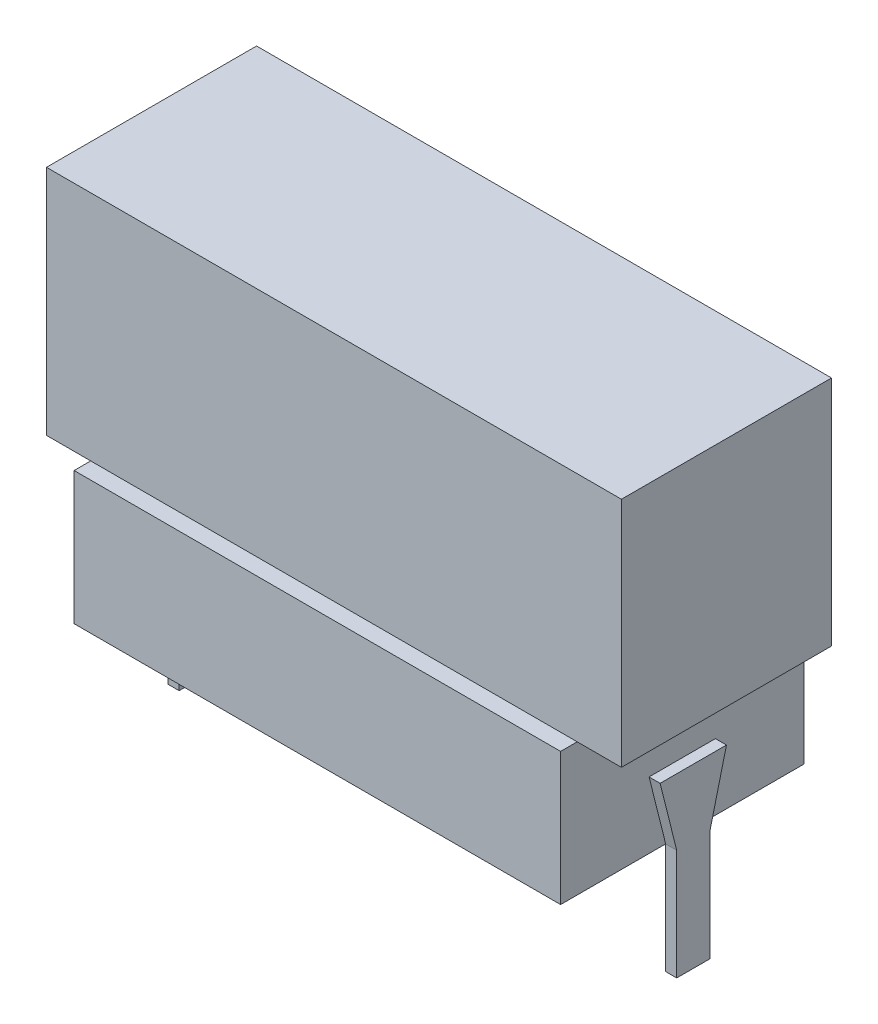
SolidWorks part; units mm, degrees
ref_plane "前视" through (0, 0, 0) normal (0, 0, 1) x (1, 0, 0)
ref_plane "上视" through (0, 0, 0) normal (0, 1, 0) x (1, 0, 0)
ref_plane "右视" through (0, 0, 0) normal (1, 0, 0) x (0, 0, -1)
sketch "草图1" plane through (0, 0, 0) normal (0, 1, 0) x (1, 0, 0)
  line L0 (-28.3755, 0) -> (18.4931, 0) construction
  line L1 (-11, 5.5) -> (11, 5.5)
  line L2 (-11, 5.5) -> (-11, -5.5)
  line L3 (-11, -5.5) -> (11, -5.5)
  line L4 (11, 5.5) -> (11, -5.5)
  line L5 (0, 15.354) -> (0, -11.4281) construction
  dimension "D1" = 22
  dimension "D2" = 11
extrude "凸台-拉伸1" add sketch "草图1" along normal blind 6
sketch "草图3" plane through (11, 11, 0) normal (-1, 0, 0) x (0, -1, 0)
  line L0 (8, 1.5) -> (8, -1.5)
  line L1 (8, -1.5) -> (11, -0.75)
  line L2 (11, 5.5) -> (11, -5.5) construction
  line L3 (11, -0.75) -> (16, -0.75)
  line L4 (16, -0.75) -> (16, 0.75)
  line L5 (16, 0.75) -> (11, 0.75)
  line L6 (11, 0.75) -> (8, 1.5)
  line L7 (9.2948, 0) -> (12.7052, 0) construction
  point P12 (11, 0)
  dimension "D1" = 1.5
  dimension "D2" = 3
  dimension "D3" = 5
  dimension "D4" = 3
extrude "凸台-拉伸3" add sketch "草图3" against normal blind 0.5
mirror "镜向3" about plane through (0, 0, 0) normal (1, 0, 0) of "凸台-拉伸3"
sketch "草图7" plane through (0, 0, 0) normal (1, 0, 0) x (0, 0, -1)
  line L0 (2.9, 6) -> (2.9, 7.4)
  line L1 (5.5, 6) -> (-5.5, 6) construction
  line L2 (0, -19.836) -> (0, 19.836) construction
  line L3 (2.7, 6) -> (2.7, 7.4)
  line L4 (2, 14.3639) -> (1.8673, 14.5136)
  line L5 (2.7, 6) -> (2.9, 6)
  line L6 (-2.7, 6) -> (-2.9, 6)
  line L7 (-2, 14.3639) -> (-1.8673, 14.5136)
  line L8 (-2.7, 6) -> (-2.7, 7.4)
  line L9 (-2.9, 6) -> (-2.9, 7.4)
  arc A0 (2.7, 7.4) -> (2.4537, 7.6952) centre (2.4, 7.4) ccw
  arc A1 (2.0875, 8.8453) -> (2.4894, 7.8919) centre (2.6, 8.5) ccw
  arc A3 (1.9345, 8.9758) -> (2.4537, 7.6952) centre (2.6, 8.5) ccw
  arc A4 (2.9, 7.4) -> (2.4894, 7.8919) centre (2.4, 7.4) ccw
  arc A5 (1.998, 13.2378) -> (2, 14.3639) centre (2.5, 13.8) cw
  arc A6 (2.0875, 8.8453) -> (1.998, 13.2378) centre (0, 11) ccw
  arc A7 (1.9345, 8.9758) -> (1.8648, 13.0886) centre (0, 11) ccw
  arc A8 (1.8648, 13.0886) -> (1.8673, 14.5136) centre (2.5, 13.8) cw
  arc A9 (-1.8648, 13.0886) -> (-1.8673, 14.5136) centre (-2.5, 13.8) ccw
  arc A10 (-1.9345, 8.9758) -> (-1.8648, 13.0886) centre (0, 11) cw
  arc A11 (-2.0875, 8.8453) -> (-1.998, 13.2378) centre (0, 11) cw
  arc A12 (-1.998, 13.2378) -> (-2, 14.3639) centre (-2.5, 13.8) ccw
  arc A13 (-2.9, 7.4) -> (-2.4894, 7.8919) centre (-2.4, 7.4) cw
  arc A14 (-1.9345, 8.9758) -> (-2.4537, 7.6952) centre (-2.6, 8.5) cw
  arc A15 (-2.0875, 8.8453) -> (-2.4894, 7.8919) centre (-2.6, 8.5) cw
  arc A16 (-2.7, 7.4) -> (-2.4537, 7.6952) centre (-2.4, 7.4) cw
  point P18 (0, 0)
  point P37 (0, 0)
  dimension "D2" = 0.5
  dimension "D12" = 3
  dimension "D3" = 2.9
  dimension "D4" = 1.4
  dimension "D5" = 2.5
  dimension "D6" = 2.5
  dimension "D7" = 7.8
  dimension "D8" = 2
  dimension "D9" = 2.6
  dimension "D11" = 5
  dimension "D10" = 0.2
extrude "凸台-拉伸5" add sketch "草图7" along normal mid plane 21
sketch "草图8" plane through (0, 0, 0) normal (0, 0, 1) x (1, 0, 0)
  line L0 (-11, 6) -> (11, 6) construction
  line L1 (-5, 14.5136) -> (5, 14.5136)
  line L2 (-5, 14.5136) -> (-5, 6)
  line L3 (-5, 6) -> (5, 6)
  line L4 (5, 14.5136) -> (5, 6)
  line L5 (10.5, 14.5136) -> (-10.5, 14.5136) construction
  line L6 (0, 0) -> (0, 10.3417) construction
  dimension "D1" = 10
extrude "切除-拉伸1" cut sketch "草图8" against normal through all both and the other way through all
sketch "草图6" plane through (0, 0, 0) normal (1, 0, 0) x (0, 0, -1)
  line L1 (5.5, 6) -> (-5.5, 6) construction
  circle A0 centre (0, 11) radius 2.5
  dimension "D1" = 5
  dimension "D2" = 5
extrude "凸台-拉伸4" add sketch "草图6" along normal mid plane 19
sketch "草图9" plane through (0, 6, 0) normal (0, 1, 0) x (1, 0, 0)
  line L0 (-5, 2.543) -> (-5, -2.5)
  line L1 (-9.5, -2.5) -> (9.5, -2.5) construction
  line L2 (-5, -2.5) -> (5, -2.5)
  line L3 (5, -2.5) -> (5, 2.543)
  line L4 (0, 4.6728) -> (0, -4.6728) construction
  point P10 (0, 0)
  dimension "D1" = 10
split line "分割线1"
sketch "草图2" plane through (0, 6, 0) normal (0, 1, 0) x (1, 0, 0)
  line L0 (0, 12.4393) -> (0, -11.6854) construction
  line L1 (-13, 4.75) -> (13, 4.75)
  line L2 (-13, 4.75) -> (-13, -4.75)
  line L3 (-13, -4.75) -> (13, -4.75)
  line L4 (13, 4.75) -> (13, -4.75)
  line L5 (-22.6876, 0) -> (17.269, 0) construction
  dimension "D1" = 26
  dimension "D2" = 9.5
extrude "凸台-拉伸2" add sketch "草图2" along normal offset from surface (10.5 mm away) 16.5 separate body up to face at (0, 0, 0)
